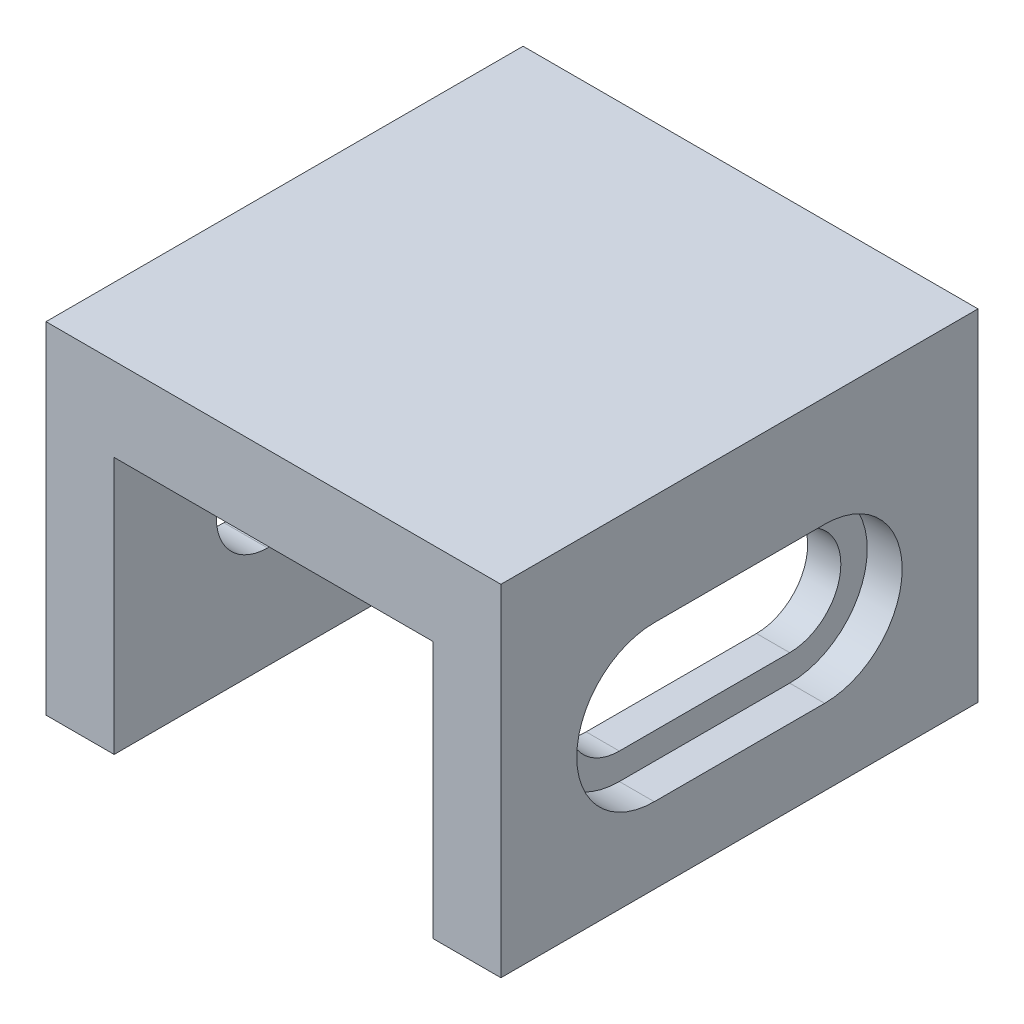
SolidWorks part; units mm, degrees
ref_plane "Front Plane" through (0, 0, 0) normal (0, 0, 1) x (1, 0, 0)
ref_plane "Top Plane" through (0, 0, 0) normal (0, 1, 0) x (1, 0, 0)
ref_plane "Right Plane" through (0, 0, 0) normal (1, 0, 0) x (0, 0, -1)
sketch "Sketch1" plane through (0, 0, 0) normal (0, 1, 0) x (1, 0, 0)
  line L1 (0, 0) -> (26.7, 0)
  line L2 (0, 0) -> (0, 28)
  line L3 (0, 28) -> (26.7, 28)
  line L4 (26.7, 0) -> (26.7, 28)
  dimension "D1" = 26.7
  dimension "D2" = 28
extrude "Boss-Extrude1" add sketch "Sketch1" along normal blind 20
sketch "Sketch2" plane through (0, 0, 0) normal (-1, 0, 0) x (0, 0, 1)
  line L0 (0, 20) -> (0, 0) construction
  line L1 (-28, 0) -> (0, 0) construction
  line L2 (-28, 20) -> (-28, 0) construction
  line L4 (-19, 12) -> (-9, 12)
  line L6 (-19, 6) -> (-9, 6)
  arc A0 (-9, 6) -> (-9, 12) centre (-9, 9) ccw
  arc A1 (-19, 12) -> (-19, 6) centre (-19, 9) ccw
  dimension "D1" = 6
  dimension "D4" = 9
  dimension "D6" = 6
  dimension "D2" = 9
  dimension "D5" = 9
extrude "Cut-Extrude1" cut sketch "Sketch2" against normal blind 27.5
sketch "Sketch3" plane through (0, 0, 0) normal (-1, 0, 0) x (0, 0, 1)
  line L1 (-19, 13.55) -> (-9, 13.55)
  line L3 (-19, 4.45) -> (-9, 4.45)
  arc A0 (-9, 4.45) -> (-9, 13.55) centre (-9, 9) ccw
  arc A1 (-19, 13.55) -> (-19, 4.45) centre (-19, 9) ccw
  dimension "D1" = 9.1
  dimension "D2" = 9.1
extrude "Cut-Extrude2" cut sketch "Sketch3" against normal blind 1.45
sketch "Sketch4" plane through (26.7, 0, 0) normal (1, 0, 0) x (0, 0, -1)
  line L1 (9, 13.55) -> (19, 13.55)
  line L3 (9, 4.45) -> (19, 4.45)
  arc A0 (9, 13.55) -> (9, 4.45) centre (9, 9) ccw
  arc A1 (19, 4.45) -> (19, 13.55) centre (19, 9) ccw
  dimension "D1" = 9.1
  dimension "D2" = 9.1
extrude "Cut-Extrude3" cut sketch "Sketch4" against normal blind 2.05
sketch "Sketch5" plane through (0, 0, 0) normal (0, 1, 0) x (1, 0, 0)
  line L0 (26.7, 28) -> (0, 28) construction
  line L1 (4, 28) -> (22.7, 28)
  line L2 (4, 28) -> (4, 0)
  line L3 (4, 0) -> (22.7, 0)
  line L4 (22.7, 28) -> (22.7, 0)
  line L5 (0, 0) -> (26.7, 0) construction
  line L6 (0, 28) -> (0, 0) construction
  line L7 (26.7, 0) -> (26.7, 28) construction
  dimension "D1" = 4
  dimension "D2" = 4
extrude "Cut-Extrude4" cut sketch "Sketch5" along normal blind 15.1
